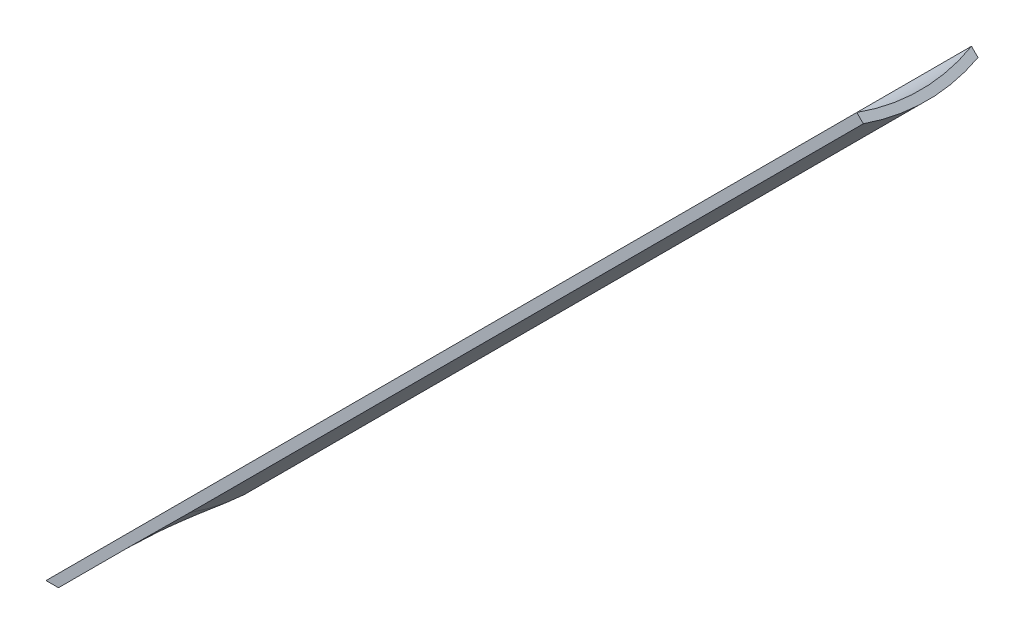
SolidWorks part; units mm, degrees
ref_plane "Front Plane" through (0, 0, 0) normal (0, 0, 1) x (1, 0, 0)
ref_plane "Top Plane" through (0, 0, 0) normal (0, 1, 0) x (1, 0, 0)
ref_plane "Right Plane" through (0, 0, 0) normal (1, 0, 0) x (0, 0, -1)
sketch "Sketch1" plane through (0, 0, 0) normal (0, 0, 1) x (1, 0, 0)
  line L0 (0.3536, 0) -> (-0.3536, 0)
  line L1 (0.3536, 0) -> (4.2426, 3.8891)
  line L4 (4.2426, 3.8891) -> (3.8891, 4.2426)
  line L5 (3.8891, 4.2426) -> (-0.3536, 0)
  point P4 (0, 0)
  dimension "D1" = 45
  dimension "D2" = 0.5
  dimension "D3" = 6
extrude "Boss-Extrude1" add sketch "Sketch1" along normal blind 6.5
sketch "Sketch2" plane through (4.0659, 4.0659, 0) normal (0.7071, 0.7071, 0) x (0, 0, -1)
  line L4 (0, -0.25) -> (0, 0.25)
  line L5 (0, 0.25) -> (-6.5, 0.25)
  line L6 (-6.5, 0.25) -> (-6.5, -0.25)
  line L7 (-6.5, -0.25) -> (0, -0.25)
  line L8 (0, -0.25) -> (0, 0.25)
  line L9 (0, 0.25) -> (-6.5, 0.25)
  line L10 (-6.5, 0.25) -> (-6.5, -0.25)
  line L11 (-6.5, -0.25) -> (0, -0.25)
  dimension "D1" = 0
ref_plane "Plane1" through (7.6014, 7.6014, 0) normal (0.7071, 0.7071, 0) x (0, 0, -1)
sketch "Sketch3" plane through (7.6014, 7.6014, 0) normal (0.7071, 0.7071, 0) x (0, 0, -1)
  line L0 (-6.5, 0.25) -> (-6.5, -0.2731)
  line L1 (0, 0.25) -> (0, -0.2731)
  line L4 (0, -0.25) -> (0, 0.25)
  line L5 (0, 0.25) -> (-6.5, 0.25)
  line L6 (-6.5, 0.25) -> (-6.5, -0.25)
  line L7 (-6.5, -0.25) -> (0, -0.25)
  line L8 (0, -0.25) -> (0, 0.25) construction
  line L9 (0, 0.25) -> (-6.5, 0.25) construction
  line L10 (-6.5, 0.25) -> (-6.5, -0.25) construction
  line L11 (-6.5, -0.25) -> (0, -0.25) construction
  arc A0 (-6.5, 0.25) -> (0, 0.25) centre (-3.25, 10.5625) ccw
  arc A1 (-6.5, -0.2731) -> (0, -0.2731) centre (-3.25, 10.5625) ccw
  arc A2 (-6.6503, -0.2269) -> (0.1503, -0.2269) centre (-3.25, 10.5625) ccw construction
  dimension "D1" = 0
  dimension "D2" = 0.5
loft "Loft1" add profiles "Sketch2", "Sketch3" connector at (3.8891, 4.2426, 6.5) connector at (7.4246, 7.7782, 6.5)
sketch "Sketch4" plane through (7.6014, 7.6014, 0) normal (0.7071, 0.7071, 0) x (0, 0, -1)
  line L2 (-6.5, 0.25) -> (-6.5, -0.2731)
  line L3 (0, -0.2731) -> (0, 0.25)
  line L4 (-6.5, 0.25) -> (-6.5, -0.2731)
  line L5 (0, -0.2731) -> (0, 0.25)
  arc A2 (-6.5, 0.25) -> (0, 0.25) centre (-3.25, 10.5625) ccw
  arc A3 (-6.5, -0.2731) -> (0, -0.2731) centre (-3.25, 10.5625) ccw
  arc A4 (-6.5, 0.25) -> (0, 0.25) centre (-3.25, 10.5625) ccw
  arc A5 (-6.5, -0.2731) -> (0, -0.2731) centre (-3.25, 10.5625) ccw
  dimension "D1" = 0
extrude "Boss-Extrude2" add sketch "Sketch4" along normal blind 54
sketch "Sketch5" [suppressed] plane through (7.6014, 7.6014, 0) normal (0.7071, 0.7071, 0) x (0, 0, -1)
  line L2 (-6.5, 0.25) -> (-6.5, -0.2731)
  line L3 (0, -0.2731) -> (0, 0.25)
  line L4 (-6.5, 0.25) -> (-6.5, -0.2731)
  line L5 (0, -0.2731) -> (0, 0.25)
  arc A2 (-6.5, 0.25) -> (0, 0.25) centre (-3.25, 10.5625) ccw
  arc A3 (-6.5, -0.2731) -> (0, -0.2731) centre (-3.25, 10.5625) ccw
  arc A4 (-6.5, 0.25) -> (0, 0.25) centre (-3.25, 10.5625) ccw
  arc A5 (-6.5, -0.2731) -> (0, -0.2731) centre (-3.25, 10.5625) ccw
  dimension "D1" = 0
extrude "Boss-Extrude3" [suppressed] add sketch "Sketch5" along normal blind 20
sketch "Sketch6" [suppressed] plane through (7.6014, 7.6014, 0) normal (0.7071, 0.7071, 0) x (0, 0, -1)
  line L2 (-6.5, 0.25) -> (-6.5, -0.2731)
  line L3 (0, -0.2731) -> (0, 0.25)
  line L4 (-6.5, 0.25) -> (-6.5, -0.2731)
  line L5 (0, -0.2731) -> (0, 0.25)
  arc A2 (-6.5, 0.25) -> (0, 0.25) centre (-3.25, 10.5625) ccw
  arc A3 (-6.5, -0.2731) -> (0, -0.2731) centre (-3.25, 10.5625) ccw
  arc A4 (-6.5, 0.25) -> (0, 0.25) centre (-3.25, 10.5625) ccw
  arc A5 (-6.5, -0.2731) -> (0, -0.2731) centre (-3.25, 10.5625) ccw
  dimension "D1" = 0
extrude "Boss-Extrude4" [suppressed] add sketch "Sketch6" along normal blind 252
